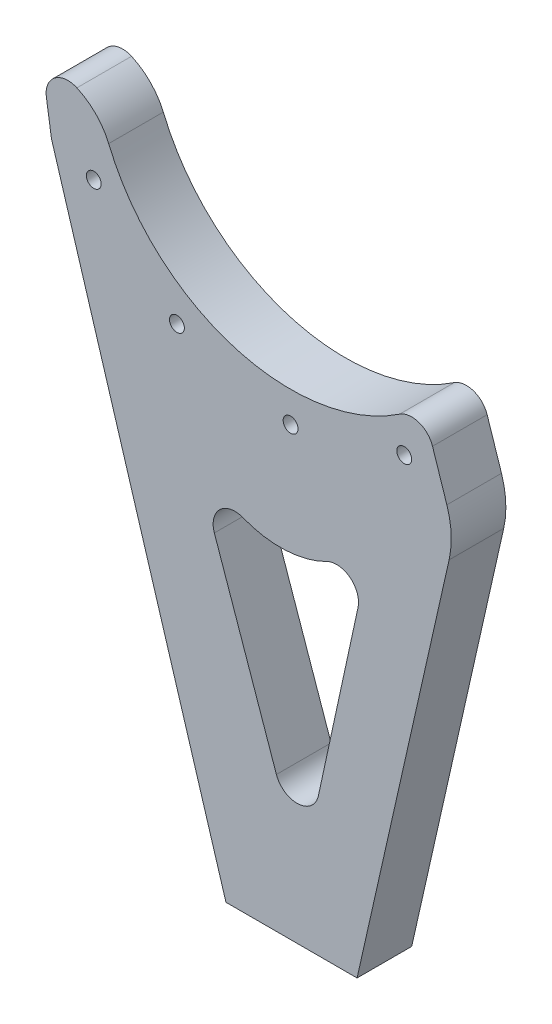
SolidWorks part; units mm, degrees
ref_plane "Front Plane" through (0, 0, 0) normal (0, 0, 1) x (1, 0, 0)
ref_plane "Top Plane" through (0, 0, 0) normal (0, 1, 0) x (1, 0, 0)
ref_plane "Right Plane" through (0, 0, 0) normal (1, 0, 0) x (0, 0, -1)
sketch "Sketch1" plane through (0, 0, 0) normal (0, 0, 1) x (1, 0, 0)
  line L1 (52, 0) -> (57.5, 0)
  line L2 (-56.8494, -8.625) -> (-54.7139, -22.7011)
  line L4 (-14.7864, -154.0477) -> (15.2136, -154.0477)
  line L5 (30.2586, -33.3079) -> (37.4888, -55.2692)
  line L7 (-14.7864, -154.0477) -> (15.2136, -154.0477)
  line L9 (-54.7139, -22.7011) -> (-14.7864, -154.0477)
  line L10 (37.4888, -55.2692) -> (15.2136, -154.0477)
  arc A1 (-41.6158, -17.1208) -> (30.2586, -33.3079) centre (0, 0) ccw
  arc A3 (-51.2334, -8.8959) -> (32.6241, -40.4928) centre (0, 0) ccw construction
  arc A6 (-51.2334, -8.8959) -> (32.6241, -40.4928) centre (0, 0) ccw construction
  arc A8 (-51.2334, -8.8959) -> (0, -52) centre (0, 0) ccw construction
  arc A11 (-56.8494, -8.625) -> (-41.6158, -17.1208) centre (-54.7139, -22.7011) cw
  circle A13 centre (0, -52) radius 1.7
  circle A14 centre (-26, -45.0333) radius 1.7
  circle A15 centre (-45.0333, -26) radius 1.7
  circle A24 centre (26, -45.0333) radius 1.7
  circle A25 centre (-45.0333, 26) radius 1.7 [skipped]
  circle A26 centre (-26, 45.0333) radius 1.7 [skipped]
  circle A27 centre (0, 52) radius 1.7 [skipped]
  circle A28 centre (45.0333, 26) radius 1.7 [skipped]
  circle A29 centre (26, 45.0333) radius 1.7 [skipped]
  arc A30 (-51.9722, -1.6998) -> (-50.3, 0) centre (-52, 0) ccw [skipped]
  arc A31 (50.3, 0) -> (51.9722, -1.6998) centre (52, 0) ccw [skipped]
  arc A32 (56.874, -8.4618) -> (57.5, 0) centre (0, 0) ccw
  circle A33 centre (45.0333, -26) radius 1.7 [skipped]
  point P26 (0, 0)
  point P32 (0, 0)
  point P50 (0, 0)
  dimension "D1" = 90
  dimension "D5" = 104
  dimension "D6" = 3.4
  dimension "D4" = 30
  dimension "D7" = 3
  dimension "D8" = 12
extrude "Boss-Extrude1" add sketch "Sketch1" along normal blind 12.5 contours A32 L1 A1 L2 A13 A14 A15 A24 region at (-5.673, -84.2355, 0)
fillet "Fillet4" radius 5 1 edges at (-56.8494, -8.625, 6.25)
fillet "Fillet5" radius 5 1 edges at (-54.7139, -22.7011, 6.25)
fillet "Fillet6" radius 5 1 edges at (30.2586, -33.3079, 6.25)
fillet "Fillet7" radius 20 1 edges at (37.4888, -55.2692, 6.25)
sketch "Sketch2" plane through (0, -154.0477, 0) normal (0, -1, 0) x (-1, 0, 0)
  line L0 (-15.2136, 0) -> (14.7864, -12.5) construction
  circle A0 centre (-0.2136, -6.25) radius 1.745
  dimension "D1" = 3.49
extrude "Cut-Extrude1" cut sketch "Sketch2" against normal blind 10
sketch "Sketch3" plane through (0, 0, 0) normal (0, 0, -1) x (-1, 0, 0)
  line L0 (-19.0101, -64.0145) -> (-2.6019, -139.7266)
  line L1 (-2.6019, -139.7266) -> (24.5888, -61.6705)
  arc A0 (24.5888, -61.6705) -> (-19.0101, -64.0145) centre (2.3091, -53.9093) cw
extrude "Cut-Extrude2" cut sketch "Sketch3" against normal blind 35
fillet "Fillet8" radius 5 1 edges at (2.6019, -139.7266, 6.25)
fillet "Fillet9" radius 5 2 edges at (-24.5888, -61.6705, 6.25) (19.0101, -64.0145, 6.25)
